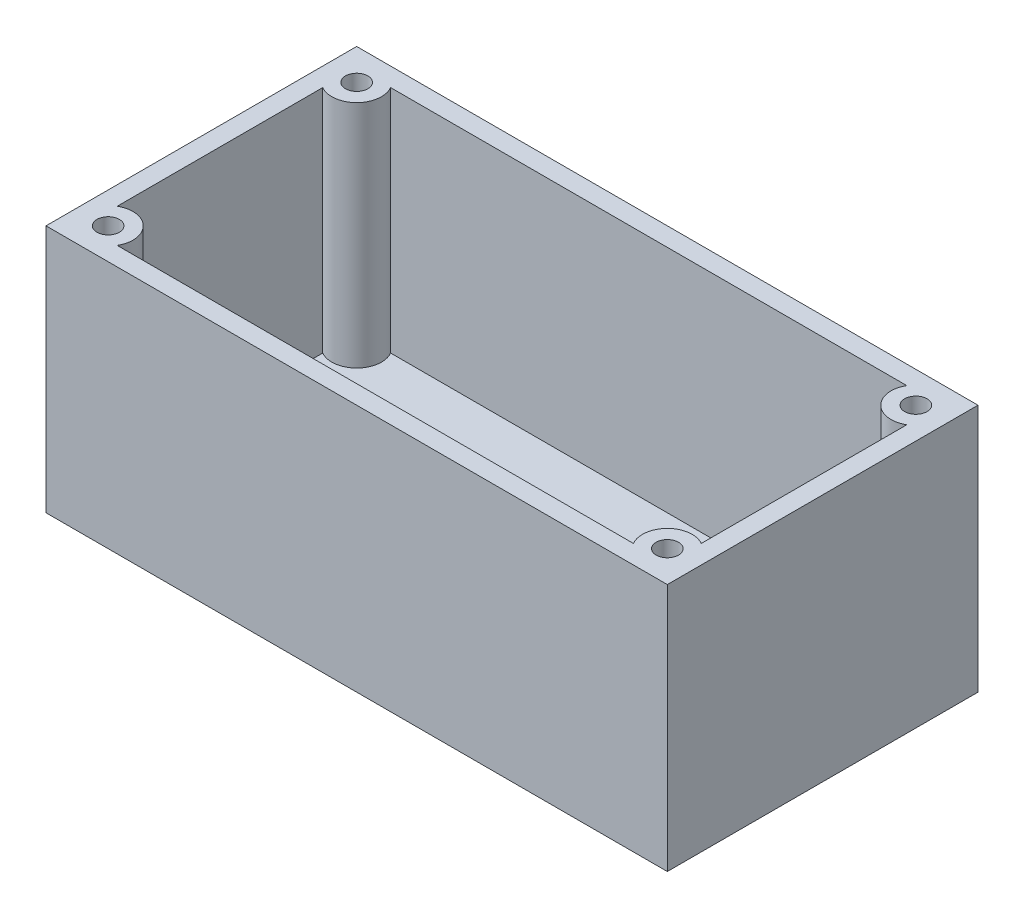
SolidWorks part; units mm, degrees
ref_plane "前视基准面" through (0, 0, 0) normal (0, 0, 1) x (1, 0, 0)
ref_plane "上视基准面" through (0, 0, 0) normal (0, 1, 0) x (1, 0, 0)
ref_plane "右视基准面" through (0, 0, 0) normal (1, 0, 0) x (0, 0, -1)
sketch "草图1" plane through (0, 0, 0) normal (0, 1, 0) x (1, 0, 0)
  line L1 (0, 0) -> (50, 0)
  line L2 (0, 0) -> (0, 25)
  line L3 (0, 25) -> (50, 25)
  line L4 (50, 0) -> (50, 25)
  circle A0 centre (2.5, 22.5) radius 2
  circle A1 centre (2.5, 22.5) radius 0.9
  circle A2 centre (47.5, 22.5) radius 2
  circle A3 centre (47.5, 22.5) radius 0.9
  circle A4 centre (47.5, 2.5) radius 2
  circle A5 centre (47.5, 2.5) radius 0.9
  circle A6 centre (2.5, 2.5) radius 2
  circle A7 centre (2.5, 2.5) radius 0.9
  dimension "D3" = 4
  dimension "D7" = 2
  dimension "D9" = 1.8
  dimension "D1" = 50
  dimension "D2" = 25
  dimension "D4" = 2.5
  dimension "D5" = 2.5
  dimension "D6" = 1.1
  dimension "D8" = 2
extrude "凸台-拉伸1" add sketch "草图1" along normal blind 20 contours A0 A1 | A6 A7 | A2 A3 | A4 A5 | A1 | A3 | A5 | A7 | L1 L4 L3 L2 A6 A4 A2 A0 region at (25, 0, -12.5) region at (0.5566, 0, -22.5) region at (2.5, 0, -22.5) region at (45.5566, 0, -22.5) region at (47.5, 0, -22.5) region at (45.5566, 0, -2.5) region at (47.5, 0, -2.5) region at (0.5566, 0, -2.5) region at (2.5, 0, -2.5)
shell "抽壳1" thickness 1.5 removed face at (25, 20, -12.5)
extrude "凸台-拉伸2" add sketch "草图1<3>" along normal blind 20 contours A0 A1 | A2 A3 | A4 A5 | A6 A7 region at (0.5566, 0, -22.5) region at (45.5566, 0, -22.5) region at (45.5566, 0, -2.5) region at (0.5566, 0, -2.5)
sketch "草图1<3>" plane through (0, 0, 0) normal (0, 1, 0) x (1, 0, 0) same geometry as "草图1"
